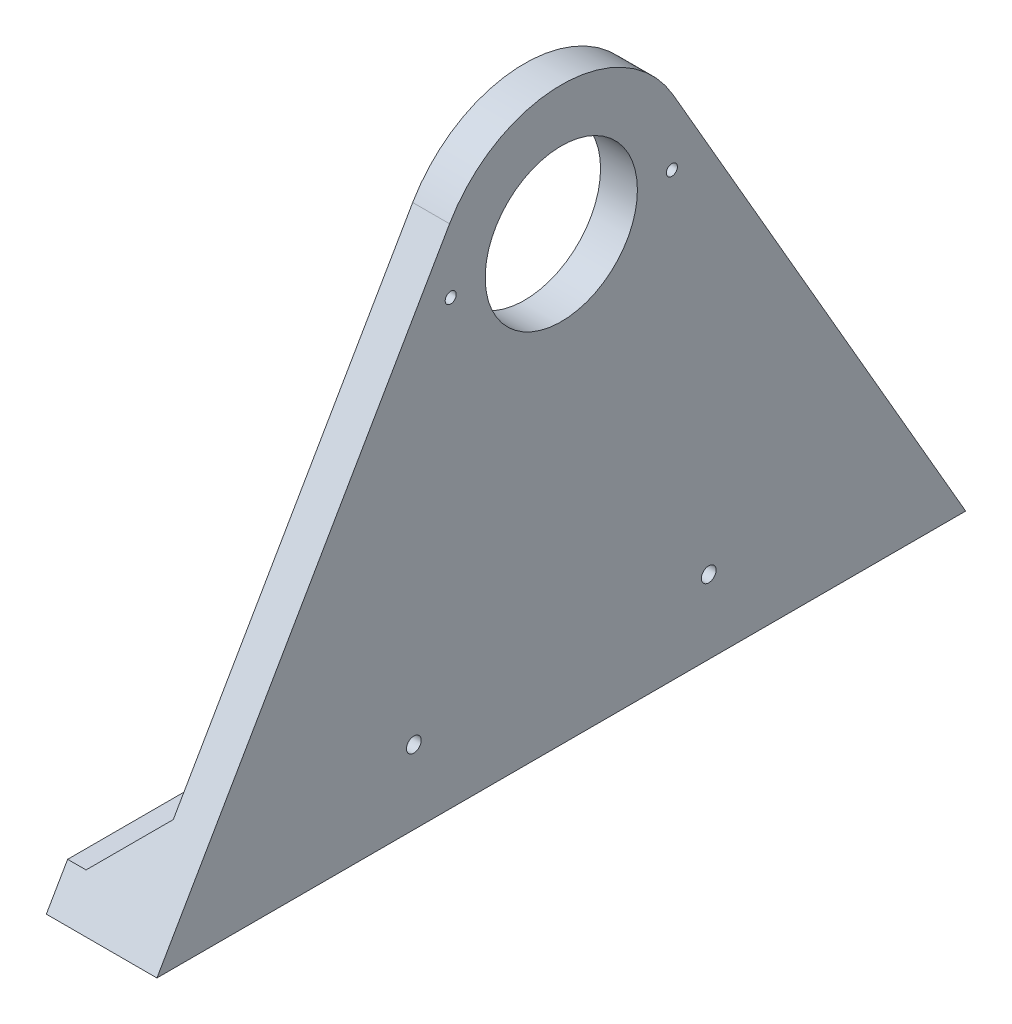
SolidWorks part; units mm, degrees
ref_plane "Alzado" through (0, 0, 0) normal (0, 0, 1) x (1, 0, 0)
ref_plane "Planta" through (0, 0, 0) normal (0, 1, 0) x (1, 0, 0)
ref_plane "Vista lateral" through (0, 0, 0) normal (1, 0, 0) x (0, 0, -1)
sketch "Croquis1" plane through (0, 0, 0) normal (1, 0, 0) x (0, 0, -1)
  line L4 (-109.6966, -120) -> (109.6966, -120)
  line L5 (-30.3109, 17.5) -> (-109.6966, -120)
  line L6 (30.3109, 17.5) -> (109.6966, -120)
  circle A2 centre (0, 0) radius 20.65
  arc A3 (30.3109, 17.5) -> (-30.3109, 17.5) centre (0, 0) ccw
  arc A4 (-30.3109, 17.5) -> (30.3109, 17.5) centre (0, 0) ccw construction
  circle A5 centre (-30, 0) radius 1.5
  circle A6 centre (30, 0) radius 1.5
  dimension "D1" = 41.3
  dimension "D6" = 3
  dimension "D3" = 70
  dimension "D7" = 3
  dimension "D2" = 120
  dimension "D4" = 60
  dimension "D5" = 60
  dimension "D8" = 30
  dimension "D9" = 60
extrude "Saliente-Extruir1" add sketch "Croquis1" along normal mid plane 10
sketch "Croquis2" plane through (-5, 0, 0) normal (-1, 0, 0) x (0, 0, 1)
  line L0 (-109.6966, -120) -> (-103.923, -110)
  line L1 (-109.6966, -120) -> (-30.3109, 17.5) construction
  line L2 (-103.923, -110) -> (103.923, -110)
  line L3 (30.3109, 17.5) -> (109.6966, -120) construction
  line L4 (103.923, -110) -> (109.6966, -120)
  line L5 (109.6966, -120) -> (-109.6966, -120)
  dimension "D1" = 10
extrude "Saliente-Extruir2" add sketch "Croquis2" along normal blind 20
sketch "Croquis3" plane through (0, -110, 0) normal (0, 1, 0) x (1, 0, 0)
  line L0 (-25, 103.923) -> (-5, 103.923) construction
  circle A0 centre (-15, 60) radius 1.5
  circle A1 centre (-15, -60) radius 1.5
  circle A2 centre (-15, 0) radius 1.5
  point P7 (-15, 103.923)
  dimension "D3" = 3
  dimension "D4" = 3
  dimension "D5" = 3
  dimension "D1" = 60
  dimension "D2" = 60
extrude "Cortar-Extruir1" cut sketch "Croquis3" against normal blind 20
sketch "Croquis4" plane through (5, 0, 0) normal (1, 0, 0) x (0, 0, -1)
  line L0 (-109.6966, -120) -> (109.6966, -120) construction
  circle A0 centre (-40, -100) radius 2
  circle A1 centre (40, -100) radius 2
  dimension "D1" = 4
  dimension "D2" = 4
  dimension "D3" = 20
  dimension "D4" = 40
  dimension "D5" = 80
extrude "Cortar-Extruir2" cut sketch "Croquis4" against normal through all
chamfer "Chaflán1" distance 15 angle 45 1 edges at (-5, -110, 0)
sketch "Croquis5" plane through (-5, 0, 0) normal (-1, 0, 0) x (0, 0, 1)
  circle A0 centre (40, -100) radius 2 construction
  circle A3 centre (40, -100) radius 2
  circle A4 centre (-40, -100) radius 2 construction
  circle A5 centre (-40, -100) radius 2
  circle A6 centre (-40, -100) radius 7
  circle A7 centre (40, -100) radius 7
  dimension "D1" = 5
extrude "Cortar-Extruir3" cut sketch "Croquis5" along normal blind 30
sketch "Croquis6" plane through (0, -110, 0) normal (0, 1, 0) x (1, 0, 0)
  circle A0 centre (-15, 60) radius 1.5 construction
  circle A1 centre (-15, 60) radius 1.5
  circle A2 centre (-15, -60) radius 1.5 construction
  circle A3 centre (-15, 0) radius 1.5 construction
  circle A4 centre (-15, -60) radius 1.5
  circle A5 centre (-15, 0) radius 1.5
  circle A6 centre (-15, 60) radius 6.5
  circle A7 centre (-15, 0) radius 6.5
  circle A8 centre (-15, -60) radius 6.5
  dimension "D2" = 5
  dimension "D3" = 5
  dimension "D4" = 5
extrude "Cortar-Extruir4" cut sketch "Croquis6" along normal blind 30
